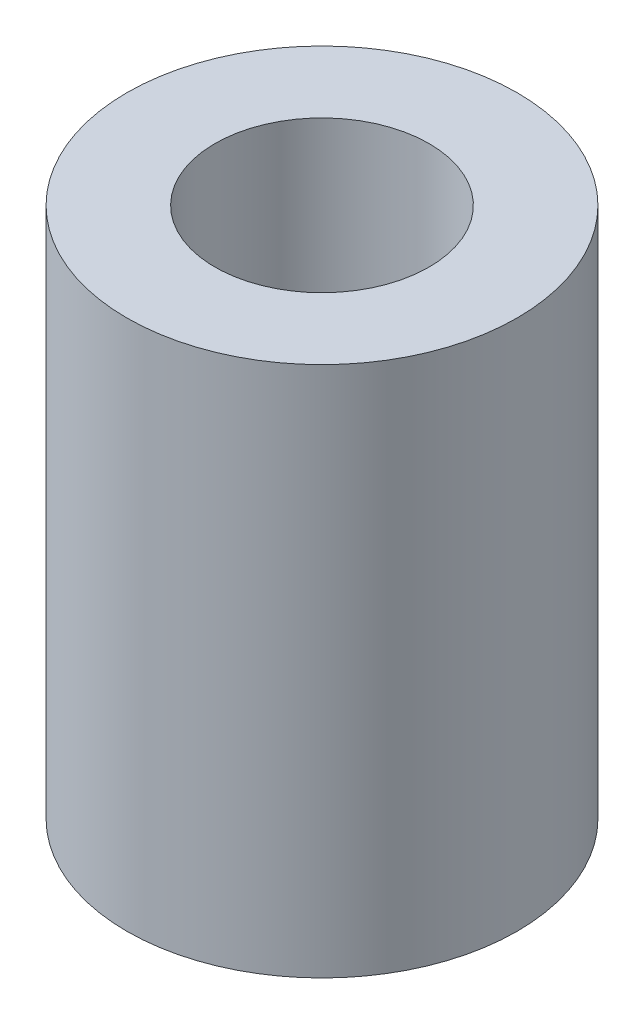
SolidWorks part; units mm, degrees
ref_plane "Front Plane" through (0, 0, 0) normal (0, 0, 1) x (1, 0, 0)
ref_plane "Top Plane" through (0, 0, 0) normal (0, 1, 0) x (1, 0, 0)
ref_plane "Right Plane" through (0, 0, 0) normal (1, 0, 0) x (0, 0, -1)
sketch "Sketch1" plane through (0, 0, 0) normal (0, 1, 0) x (1, 0, 0)
  circle A0 centre (0, 0) radius 2.7991
  circle A1 centre (0, 0) radius 1.5359
  dimension "D1" = 3.0718
extrude "Boss-Extrude1" add sketch "Sketch1" along normal blind 7.62
